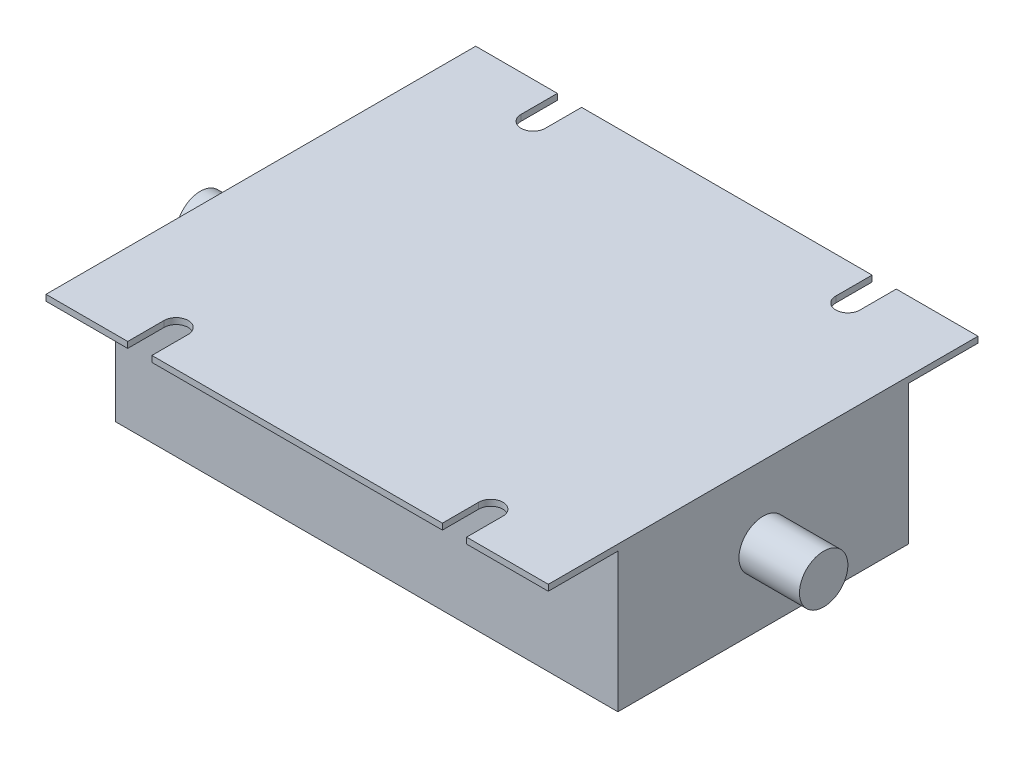
SolidWorks part; units mm, degrees
ref_plane "前基準面" through (0, 0, 0) normal (0, 0, 1) x (1, 0, 0)
ref_plane "上基準面" through (0, 0, 0) normal (0, 1, 0) x (1, 0, 0)
ref_plane "右基準面" through (0, 0, 0) normal (1, 0, 0) x (0, 0, -1)
ref_plane "平面1" through (0, 18, 0) normal (0, 1, 0) x (1, 0, 0)
sketch "草圖1" plane through (0, 18, 0) normal (0, 1, 0) x (1, 0, 0)
  line L0 (41.5, -24) -> (41.5, 24)
  line L1 (41.5, 24) -> (-41.5, 24)
  line L2 (-41.5, 24) -> (-41.5, -24)
  line L3 (-41.5, -24) -> (41.5, -24)
  line L4 (-41.5, 24) -> (41.5, -24) construction
  line L5 (41.5, 24) -> (-41.5, -24) construction
  point P4 (0, 0)
  point P5 (0, 0)
  dimension "D1" = 83
  dimension "D2" = 48
extrude "填料-伸長1" add sketch "草圖1" against normal blind 24
sketch "草圖21" plane through (0, 0, 0) normal (0, 0, -1) x (-1, 0, 0)
  line L0 (-41.5, 18) -> (41.5, 18)
  line L1 (41.5, 18) -> (41.5, 17)
  line L2 (41.5, 17) -> (-41.5, 17)
  line L3 (-41.5, 17) -> (-41.5, 18)
  line L4 (-41.5, -6) -> (-41.5, 18) construction
  line L5 (41.5, -6) -> (41.5, 18) construction
  line L6 (55, 18) -> (-55, 18) construction
  dimension "D1" = 1
extrude "填料-伸長2" add sketch "草圖21" along normal mid plane 71
sketch "草圖22" plane through (0, 18, 0) normal (0, 1, 0) x (-1, 0, 0)
  line L0 (41.5, -35.5) -> (-41.5, -35.5) construction
  line L1 (-28, -43.1015) -> (-24, -43.1015)
  line L2 (-28, -43.1015) -> (-28, -29.5)
  line L3 (-28, -29.5) -> (-24, -29.5)
  line L4 (-24, -43.1015) -> (-24, -29.5)
  line L5 (-28, -43.1015) -> (-24, -29.5) construction
  line L6 (-28, -29.5) -> (-24, -43.1015) construction
  line L7 (0, 0) -> (0, -47.7547) construction
  circle A0 centre (-26, -29.5) radius 2
  point P2 (-26, -36.3007)
  point P9 (-26, -29.5)
  point P10 (0, 0)
  line M5 (-41.5, -35.5) -> (41.5, -35.5)
  dimension "D1" = 4
  dimension "D2" = 6
  dimension "D3" = 52
extrude "除料-伸長20" cut sketch "草圖22" against normal through all contours L3 A0 | L3 A0 | A0 L2 L4 M5 region at (26, 18, -33.2629) region at (26, 18, -28.6512) region at (26, 18, -30.3488)
mirror "鏡射1" about plane through (0, 0, 0) normal (1, 0, 0) of "除料-伸長20"
mirror "鏡射2" about plane through (0, 0, 0) normal (0, 0, 1) of "鏡射1"
sketch "草圖27" plane through (-41.5, 0, 0) normal (-1, 0, 0) x (0, 0, 1)
  line L1 (55, 18) -> (-55, 18) construction
  circle A0 centre (0, 6) radius 4
  dimension "D1" = 8
  dimension "D2" = 12
extrude "填料-伸長4" add sketch "草圖27" along normal blind 10
mirror "鏡射3" about plane through (0, 0, 0) normal (1, 0, 0) of "填料-伸長4"
